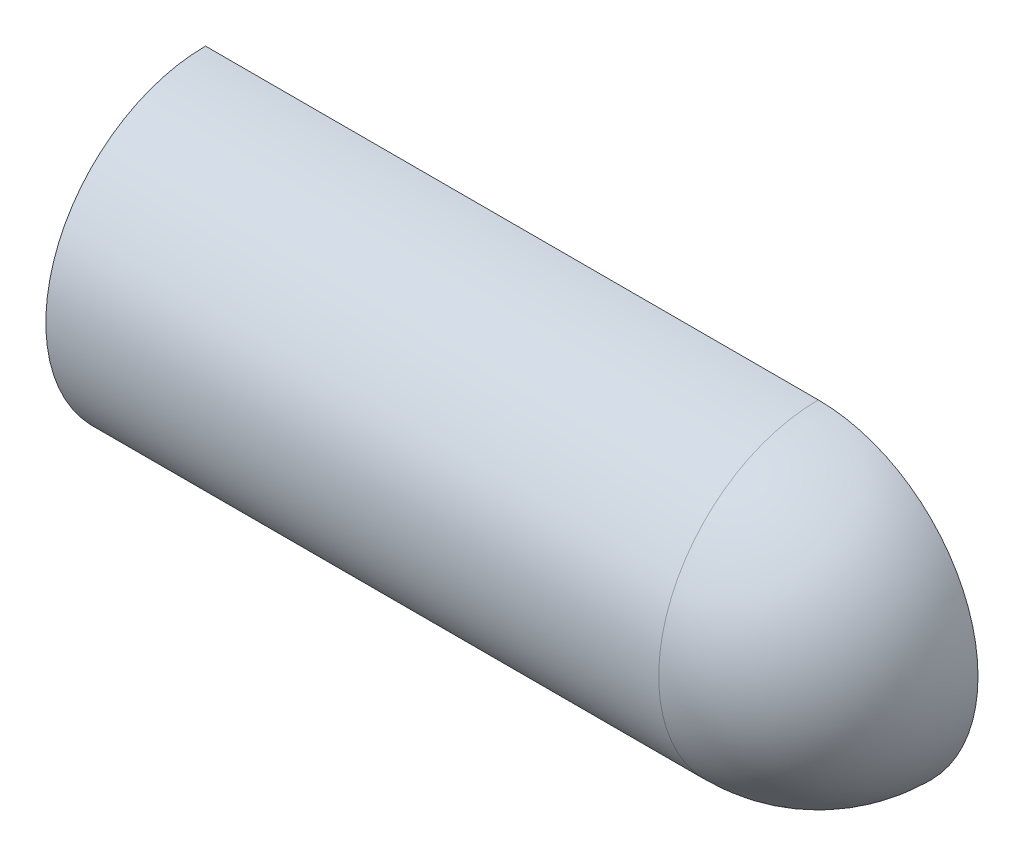
SolidWorks part; units mm, degrees
ref_plane "Front Plane" through (0, 0, 0) normal (0, 0, 1) x (1, 0, 0)
ref_plane "Top Plane" through (0, 0, 0) normal (0, 1, 0) x (1, 0, 0)
ref_plane "Right Plane" through (0, 0, 0) normal (1, 0, 0) x (0, 0, -1)
sketch "Sketch2" plane through (0, 0, 0) normal (0, 0, 1) x (1, 0, 0)
  line L0 (26, 0) -> (31, 0)
  line L2 (-119, 31) -> (0, 31)
  line L3 (-119, 31) -> (-119, 26)
  line L4 (0, 26) -> (-119, 26)
  arc A0 (-5.1991, -30.5609) -> (5.1991, 30.5609) centre (0, 0) ccw construction
  circle A1 centre (0, 0) radius 31 construction
  arc A3 (31, 0) -> (0, 31) centre (0, 0) ccw
  arc A4 (26, 0) -> (0, 26) centre (0, 0) ccw
revolve "Revolve1" add sketch "Sketch2" angle 180 about L0
